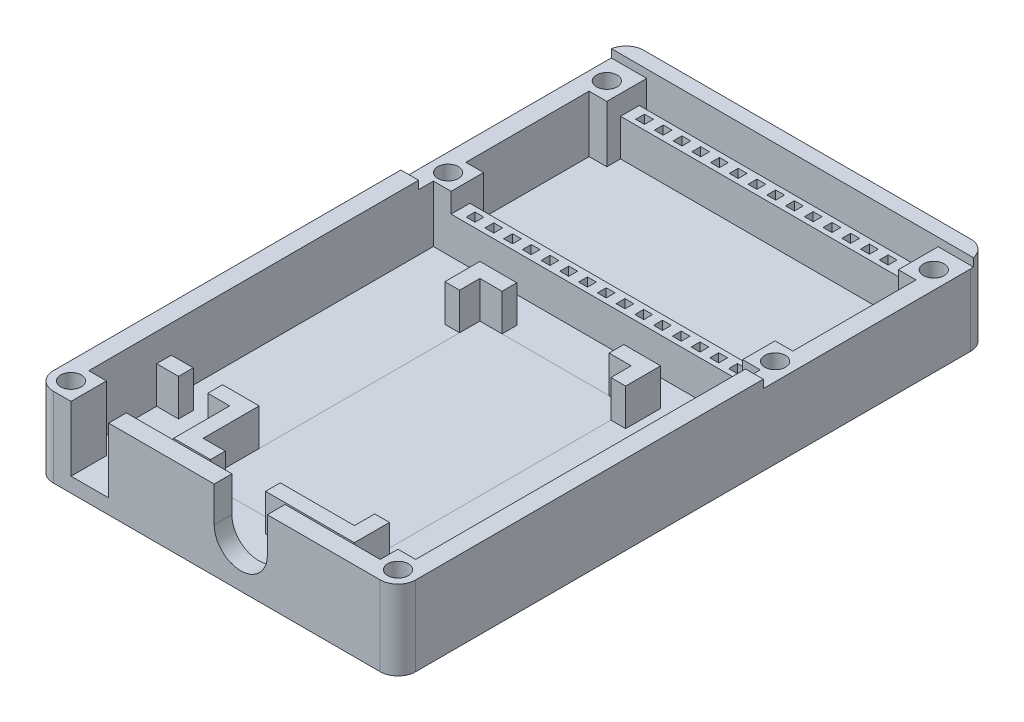
SolidWorks part; units mm, degrees
ref_plane "Front Plane" through (0, 0, 0) normal (0, 0, 1) x (1, 0, 0)
ref_plane "Top Plane" through (0, 0, 0) normal (0, 1, 0) x (1, 0, 0)
ref_plane "Right Plane" through (0, 0, 0) normal (1, 0, 0) x (0, 0, -1)
sketch "Sketch1" plane through (0, 0, 0) normal (0, 1, 0) x (1, 0, 0)
  line L1 (0, 0) -> (49.1, 0)
  line L2 (0, 0) -> (0, -80)
  line L3 (0, -80) -> (49.1, -80)
  line L4 (49.1, 0) -> (49.1, -80)
  dimension "D1" = 49.1
  dimension "D2" = 80
extrude "Boss-Extrude1" add sketch "Sketch1" along normal blind 2
sketch "Sketch2" plane through (0, 2, 0) normal (0, 1, 0) x (1, 0, 0)
  line L0 (24.55, 0) -> (24.55, -5) construction
  line L1 (2.4, -5) -> (46.7, -5) construction
  line L2 (2.4, -5) -> (2.4, -26.5) construction
  line L3 (2.4, -26.5) -> (46.7, -26.5) construction
  line L4 (46.7, -5) -> (46.7, -26.5) construction
  line L5 (49.1, 0) -> (0, 0) construction
  line L6 (0, 0) -> (0, -80) construction
  circle A0 centre (2.4, -5) radius 1.4
  circle A1 centre (46.7, -5) radius 1.4
  circle A2 centre (46.7, -26.5) radius 1.4
  circle A3 centre (2.4, -26.5) radius 1.4
  dimension "D3" = 2.8
  dimension "D1" = 44.3
  dimension "D2" = 21.5
  dimension "D4" = 5
  dimension "D5" = 2.4
extrude "Cut-Extrude1" cut sketch "Sketch2" against normal blind 2
sketch "Sketch3" plane through (0, 2, 0) normal (0, 1, 0) x (1, 0, 0)
  line L0 (2.4, -15.75) -> (46.7, -15.75) construction
  line L1 (2.4, -5) -> (46.7, -5) construction
  line L2 (2.4, -5) -> (2.4, -26.5) construction
  line L3 (2.4, -26.5) -> (46.7, -26.5) construction
  line L4 (46.7, -5) -> (46.7, -26.5) construction
  line L5 (6.17, -3.67) -> (7.37, -3.67)
  line L6 (6.17, -3.67) -> (6.17, -4.87)
  line L7 (6.17, -4.87) -> (7.37, -4.87)
  line L8 (7.37, -3.67) -> (7.37, -4.87)
  line L9 (5.5, -3) -> (8.04, -5.54) construction
  line L10 (5.5, -3) -> (8.04, -3) construction
  line L11 (5.5, -3) -> (5.5, -5.54) construction
  line L12 (5.5, -5.54) -> (8.04, -5.54) construction
  line L13 (8.04, -3) -> (8.04, -5.54) construction
  line L14 (8.04, -3) -> (5.5, -5.54) construction
  line L15 (6.17, -3.67) -> (7.37, -4.87) construction
  line L16 (8.71, -3.67) -> (9.91, -3.67)
  line L17 (8.71, -3.67) -> (8.71, -4.87)
  line L18 (9.91, -3.67) -> (9.91, -4.87)
  line L19 (8.71, -4.87) -> (9.91, -4.87)
  line L20 (11.25, -3.67) -> (12.45, -3.67)
  line L21 (11.25, -3.67) -> (11.25, -4.87)
  line L22 (12.45, -3.67) -> (12.45, -4.87)
  line L23 (11.25, -4.87) -> (12.45, -4.87)
  line L24 (13.79, -3.67) -> (14.99, -3.67)
  line L25 (13.79, -3.67) -> (13.79, -4.87)
  line L26 (14.99, -3.67) -> (14.99, -4.87)
  line L27 (13.79, -4.87) -> (14.99, -4.87)
  line L28 (16.33, -3.67) -> (17.53, -3.67)
  line L29 (16.33, -3.67) -> (16.33, -4.87)
  line L30 (17.53, -3.67) -> (17.53, -4.87)
  line L31 (16.33, -4.87) -> (17.53, -4.87)
  line L32 (18.87, -3.67) -> (20.07, -3.67)
  line L33 (18.87, -3.67) -> (18.87, -4.87)
  line L34 (20.07, -3.67) -> (20.07, -4.87)
  line L35 (18.87, -4.87) -> (20.07, -4.87)
  line L36 (21.41, -3.67) -> (22.61, -3.67)
  line L37 (21.41, -3.67) -> (21.41, -4.87)
  line L38 (22.61, -3.67) -> (22.61, -4.87)
  line L39 (21.41, -4.87) -> (22.61, -4.87)
  line L40 (23.95, -3.67) -> (25.15, -3.67)
  line L41 (23.95, -3.67) -> (23.95, -4.87)
  line L42 (25.15, -3.67) -> (25.15, -4.87)
  line L43 (23.95, -4.87) -> (25.15, -4.87)
  line L44 (26.49, -3.67) -> (27.69, -3.67)
  line L45 (26.49, -3.67) -> (26.49, -4.87)
  line L46 (27.69, -3.67) -> (27.69, -4.87)
  line L47 (26.49, -4.87) -> (27.69, -4.87)
  line L48 (29.03, -3.67) -> (30.23, -3.67)
  line L49 (29.03, -3.67) -> (29.03, -4.87)
  line L50 (30.23, -3.67) -> (30.23, -4.87)
  line L51 (29.03, -4.87) -> (30.23, -4.87)
  line L52 (31.57, -3.67) -> (32.77, -3.67)
  line L53 (31.57, -3.67) -> (31.57, -4.87)
  line L54 (32.77, -3.67) -> (32.77, -4.87)
  line L55 (31.57, -4.87) -> (32.77, -4.87)
  line L56 (34.11, -3.67) -> (35.31, -3.67)
  line L57 (34.11, -3.67) -> (34.11, -4.87)
  line L58 (35.31, -3.67) -> (35.31, -4.87)
  line L59 (34.11, -4.87) -> (35.31, -4.87)
  line L60 (36.65, -3.67) -> (37.85, -3.67)
  line L61 (36.65, -3.67) -> (36.65, -4.87)
  line L62 (37.85, -3.67) -> (37.85, -4.87)
  line L63 (36.65, -4.87) -> (37.85, -4.87)
  line L64 (39.19, -3.67) -> (40.39, -3.67)
  line L65 (39.19, -3.67) -> (39.19, -4.87)
  line L66 (40.39, -3.67) -> (40.39, -4.87)
  line L67 (39.19, -4.87) -> (40.39, -4.87)
  line L68 (41.73, -3.67) -> (42.93, -3.67)
  line L69 (41.73, -3.67) -> (41.73, -4.87)
  line L70 (42.93, -3.67) -> (42.93, -4.87)
  line L71 (41.73, -4.87) -> (42.93, -4.87)
  line L72 (6.17, -27.83) -> (7.37, -26.63) construction
  line L73 (8.04, -28.5) -> (5.5, -25.96) construction
  line L74 (8.04, -28.5) -> (8.04, -25.96) construction
  line L75 (5.5, -25.96) -> (8.04, -25.96) construction
  line L76 (5.5, -28.5) -> (5.5, -25.96) construction
  line L77 (5.5, -28.5) -> (8.04, -28.5) construction
  line L78 (5.5, -28.5) -> (8.04, -25.96) construction
  line L79 (2.4, -26.5) -> (46.7, -26.5) construction
  line L80 (41.73, -26.63) -> (42.93, -26.63)
  line L81 (42.93, -27.83) -> (42.93, -26.63)
  line L82 (41.73, -27.83) -> (41.73, -26.63)
  line L83 (41.73, -27.83) -> (42.93, -27.83)
  line L84 (39.19, -26.63) -> (40.39, -26.63)
  line L85 (40.39, -27.83) -> (40.39, -26.63)
  line L86 (39.19, -27.83) -> (39.19, -26.63)
  line L87 (39.19, -27.83) -> (40.39, -27.83)
  line L88 (36.65, -26.63) -> (37.85, -26.63)
  line L89 (37.85, -27.83) -> (37.85, -26.63)
  line L90 (36.65, -27.83) -> (36.65, -26.63)
  line L91 (36.65, -27.83) -> (37.85, -27.83)
  line L92 (34.11, -26.63) -> (35.31, -26.63)
  line L93 (35.31, -27.83) -> (35.31, -26.63)
  line L94 (34.11, -27.83) -> (34.11, -26.63)
  line L95 (34.11, -27.83) -> (35.31, -27.83)
  line L96 (31.57, -26.63) -> (32.77, -26.63)
  line L97 (32.77, -27.83) -> (32.77, -26.63)
  line L98 (31.57, -27.83) -> (31.57, -26.63)
  line L99 (31.57, -27.83) -> (32.77, -27.83)
  line L100 (29.03, -26.63) -> (30.23, -26.63)
  line L101 (30.23, -27.83) -> (30.23, -26.63)
  line L102 (29.03, -27.83) -> (29.03, -26.63)
  line L103 (29.03, -27.83) -> (30.23, -27.83)
  line L104 (26.49, -26.63) -> (27.69, -26.63)
  line L105 (27.69, -27.83) -> (27.69, -26.63)
  line L106 (26.49, -27.83) -> (26.49, -26.63)
  line L107 (26.49, -27.83) -> (27.69, -27.83)
  line L108 (23.95, -26.63) -> (25.15, -26.63)
  line L109 (25.15, -27.83) -> (25.15, -26.63)
  line L110 (23.95, -27.83) -> (23.95, -26.63)
  line L111 (23.95, -27.83) -> (25.15, -27.83)
  line L112 (21.41, -26.63) -> (22.61, -26.63)
  line L113 (22.61, -27.83) -> (22.61, -26.63)
  line L114 (21.41, -27.83) -> (21.41, -26.63)
  line L115 (21.41, -27.83) -> (22.61, -27.83)
  line L116 (18.87, -26.63) -> (20.07, -26.63)
  line L117 (20.07, -27.83) -> (20.07, -26.63)
  line L118 (18.87, -27.83) -> (18.87, -26.63)
  line L119 (18.87, -27.83) -> (20.07, -27.83)
  line L120 (16.33, -26.63) -> (17.53, -26.63)
  line L121 (17.53, -27.83) -> (17.53, -26.63)
  line L122 (16.33, -27.83) -> (16.33, -26.63)
  line L123 (16.33, -27.83) -> (17.53, -27.83)
  line L124 (13.79, -26.63) -> (14.99, -26.63)
  line L125 (14.99, -27.83) -> (14.99, -26.63)
  line L126 (13.79, -27.83) -> (13.79, -26.63)
  line L127 (13.79, -27.83) -> (14.99, -27.83)
  line L128 (11.25, -26.63) -> (12.45, -26.63)
  line L129 (12.45, -27.83) -> (12.45, -26.63)
  line L130 (11.25, -27.83) -> (11.25, -26.63)
  line L131 (11.25, -27.83) -> (12.45, -27.83)
  line L132 (8.71, -26.63) -> (9.91, -26.63)
  line L133 (9.91, -27.83) -> (9.91, -26.63)
  line L134 (8.71, -27.83) -> (8.71, -26.63)
  line L135 (8.71, -27.83) -> (9.91, -27.83)
  line L136 (7.37, -27.83) -> (7.37, -26.63)
  line L137 (6.17, -26.63) -> (7.37, -26.63)
  line L138 (6.17, -27.83) -> (6.17, -26.63)
  line L139 (6.17, -27.83) -> (7.37, -27.83)
  line L140 (0, 0) -> (0, -80) construction
  line L141 (4.8, -3) -> (44.3, -3)
  line L142 (0, -3) -> (0, -28.5)
  line L143 (0, -28.5) -> (49.1, -28.5)
  line L144 (49.1, -3) -> (49.1, -28.5)
  line L145 (49.1, -80) -> (49.1, 0) construction
  line L146 (24.55, -15.75) -> (24.55, -7.9718) construction
  line L148 (4.8, -3) -> (4.8, -2.6)
  line L149 (4.8, -2.6) -> (0, -2.6)
  line L150 (0, -3) -> (0, -2.6)
  line L151 (44.3, -2.6) -> (49.1, -2.6)
  line L152 (49.1, -3) -> (49.1, -2.6)
  line L154 (44.3, -3) -> (44.3, -2.6)
  circle A0 centre (2.4, -5) radius 1.4 construction
  circle A1 centre (2.4, -5) radius 1.4
  circle A2 centre (2.4, -26.5) radius 1.4
  circle A3 centre (46.7, -5) radius 1.4
  circle A4 centre (46.7, -26.5) radius 1.4
  circle A5 centre (2.4, -26.5) radius 1.4 construction
  point P12 (6.77, -4.27)
  point P139 (6.77, -27.23)
  dimension "D5" = 2
  dimension "D6" = 3.1
  dimension "D1" = 1.2
  dimension "D2" = 1.2
  dimension "D3" = 2.54
  dimension "D4" = 2.54
  dimension "D8" = 2.54
  dimension "D9" = 2.4
  dimension "D10" = 2.4
  dimension "D7" = 15
extrude "Boss-Extrude2" add sketch "Sketch3" along normal blind 5
sketch "Sketch4" plane through (0, 7, 0) normal (0, 1, 0) x (1, 0, 0)
  line L0 (0, -15.75) -> (49.1, -15.75) construction
  line L1 (0, -2.6) -> (0, -28.5) construction
  line L2 (49.1, -2.6) -> (44.3, -2.6) construction
  line L3 (24.55, -3) -> (24.55, -28.5) construction
  line L4 (44.3, -3) -> (4.8, -3) construction
  line L5 (0, -28.5) -> (49.1, -28.5) construction
  line L6 (0, -28.5) -> (49.1, -28.5) construction
  line L7 (0, -24.1) -> (4.8, -24.1)
  line L8 (0, -24.1) -> (0, -28.5)
  line L9 (0, -28.5) -> (4.8, -28.5)
  line L10 (4.8, -24.1) -> (4.8, -28.5)
  line L11 (49.1, -28.5) -> (44.3, -28.5)
  line L12 (44.3, -24.1) -> (44.3, -28.5)
  line L13 (49.1, -24.1) -> (44.3, -24.1)
  line L14 (49.1, -24.1) -> (49.1, -28.5)
  line L15 (49.1, -7.4) -> (49.1, -3)
  line L16 (49.1, -7.4) -> (44.3, -7.4)
  line L17 (44.3, -7.4) -> (44.3, -3)
  line L20 (4.8, -7.4) -> (4.8, -3)
  line L21 (0, -7.4) -> (4.8, -7.4)
  line L22 (0, -7.4) -> (0, -3)
  line L23 (44.3, -2.6) -> (49.1, -2.6)
  line L24 (0, -2.6) -> (4.8, -2.6)
  line L25 (0, -2.6) -> (0, -3)
  line L27 (4.8, -2.6) -> (4.8, -3)
  line L28 (44.3, -2.6) -> (44.3, -3)
  line L30 (49.1, -2.6) -> (49.1, -3)
  line L31 (49.1, -2.6) -> (49.1, 0) construction
  circle A0 centre (2.4, -5) radius 1.4 construction
  circle A1 centre (2.4, -26.5) radius 1.4
  circle A2 centre (2.4, -26.5) radius 1.4 construction
  circle A3 centre (46.7, -26.5) radius 1.4
  circle A4 centre (2.4, -5) radius 1.4
  circle A5 centre (46.7, -5) radius 1.4
  dimension "D1" = 2.4
  dimension "D2" = 2.4
extrude "Boss-Extrude3" add sketch "Sketch4" along normal blind 2.68
sketch "Sketch5" plane through (0, 2, 0) normal (0, 1, 0) x (1, 0, 0)
  line L0 (0, -52.85) -> (49.1, -52.85) construction
  line L1 (0, -80) -> (49.1, -80) construction
  line L3 (0, -28.5) -> (49.1, -28.5) construction
  line L4 (14.3, -34.1) -> (34.8, -34.1)
  line L5 (14.3, -34.1) -> (14.3, -71.6)
  line L6 (14.3, -71.6) -> (34.8, -71.6)
  line L7 (34.8, -34.1) -> (34.8, -71.6)
  line L8 (14.3, -34.1) -> (34.8, -71.6) construction
  line L9 (14.3, -71.6) -> (34.8, -34.1) construction
  line L10 (12.3, -68.85) -> (17.3, -68.85)
  line L11 (12.3, -32.1) -> (36.8, -32.1)
  line L12 (12.3, -32.1) -> (12.3, -73.6)
  line L13 (12.3, -73.6) -> (36.8, -73.6)
  line L14 (36.8, -32.1) -> (36.8, -73.6)
  line L15 (12.3, -32.1) -> (36.8, -73.6) construction
  line L16 (12.3, -73.6) -> (36.8, -32.1) construction
  line L17 (12.3, -32.1) -> (17.3, -32.1)
  line L18 (12.3, -32.1) -> (12.3, -36.85)
  line L19 (12.3, -36.85) -> (17.3, -36.85)
  line L20 (17.3, -32.1) -> (17.3, -36.85)
  line L21 (17.3, -73.6) -> (17.3, -68.85)
  line L22 (12.3, -73.6) -> (17.3, -73.6)
  line L23 (12.3, -73.6) -> (12.3, -68.85)
  line L24 (24.55, -52.85) -> (24.55, -28.5) construction
  line L25 (36.8, -36.85) -> (31.8, -36.85)
  line L26 (31.8, -32.1) -> (31.8, -36.85)
  line L27 (36.8, -32.1) -> (31.8, -32.1)
  line L28 (36.8, -32.1) -> (36.8, -36.85)
  line L29 (36.8, -73.6) -> (31.8, -73.6)
  line L30 (31.8, -73.6) -> (31.8, -68.85)
  line L31 (36.8, -68.85) -> (31.8, -68.85)
  line L32 (36.8, -73.6) -> (36.8, -68.85)
  line L33 (24.7526, -71.6) -> (24.7526, -73.6)
  line L34 (32.7526, -71.6) -> (32.7526, -73.6)
  line L35 (0, -28.5) -> (0, -80) construction
  point P6 (24.55, -52.85)
  point P13 (24.55, -52.85)
  dimension "D1" = 37.5
  dimension "D2" = 20.5
  dimension "D3" = 6.4
  dimension "D4" = 2
  dimension "D5" = 2
  dimension "D6" = 2.75
  dimension "D7" = 3
  dimension "D8" = 8
extrude "Boss-Extrude4" add sketch "Sketch5" along normal blind 5 contours L20 L11 L12 L19 L5 L4 | L11 L26 L4 L7 L25 L14 | L6 L34 L29 L14 L31 L7 | L13 L21 L6 L5 L10 L12 | L6 L33 L13 L30 | L34 L6 L30 L13 region at (14.2677, 2, 33.9427) region at (34.8323, 2, 33.9427) region at (14.2677, 2, 71.7573) region at (35.1905, 2, 71.6391) region at (28.2763, 2, 72.6) region at (32.2763, 2, 72.6)
sketch "Sketch6" plane through (0, 2, 0) normal (0, 1, 0) x (1, 0, 0)
  line L0 (0, -28.5) -> (0, -80) construction
  line L1 (0, -75.2) -> (4.8, -75.2)
  line L2 (0, -75.2) -> (0, -80)
  line L3 (0, -80) -> (4.8, -80)
  line L4 (4.8, -75.2) -> (4.8, -80)
  line L5 (0, -80) -> (49.1, -80) construction
  line L6 (24.55, -80) -> (24.55, -43.6832) construction
  line L7 (0, -80) -> (4.8, -75.2) construction
  line L8 (49.1, -80) -> (44.3, -75.2) construction
  line L9 (44.3, -75.2) -> (44.3, -80)
  line L10 (49.1, -80) -> (44.3, -80)
  line L11 (49.1, -75.2) -> (49.1, -80)
  line L12 (49.1, -75.2) -> (44.3, -75.2)
  circle A0 centre (2.4, -77.6) radius 1.4
  circle A1 centre (46.7, -77.6) radius 1.4
  dimension "D1" = 2.8
  dimension "D3" = 2.4
  dimension "D2" = 2.4
extrude "Boss-Extrude5" add sketch "Sketch6" along normal blind 8.78
sketch "Sketch7" plane through (0, 2, 0) normal (0, 1, 0) x (1, 0, 0)
  line L0 (4.8, -75.2) -> (0, -75.2) construction
  line L1 (0, -28.5) -> (2.4, -28.5)
  line L2 (0, -28.5) -> (0, -75.2)
  line L3 (0, -75.2) -> (2.4, -75.2)
  line L4 (2.4, -28.5) -> (2.4, -75.2)
  line L5 (44.3, -28.5) -> (49.1, -28.5) construction
  line L6 (49.1, -75.2) -> (46.7, -75.2)
  line L7 (49.1, -75.2) -> (49.1, -28.5)
  line L8 (49.1, -28.5) -> (46.7, -28.5)
  line L9 (46.7, -75.2) -> (46.7, -28.5)
  line L10 (49.1, -2.6) -> (49.1, 0) construction
  line L11 (0, 0) -> (49.1, 0)
  line L12 (0, 0) -> (0, -2)
  line L13 (4.8, -2) -> (44.3, -2)
  line L14 (49.1, 0) -> (49.1, -2)
  line L15 (44.3, -3) -> (4.8, -3) construction
  line L16 (4.8, -80) -> (4.8, -75.2) construction
  line L17 (4.8, -77.6) -> (44.3, -77.6)
  line L18 (4.8, -77.6) -> (4.8, -80)
  line L19 (4.8, -80) -> (44.3, -80)
  line L20 (44.3, -77.6) -> (44.3, -80)
  line L23 (0, -2) -> (0, -2.6)
  line L24 (0, -2.6) -> (4.8, -2.6)
  line L25 (4.8, -2) -> (4.8, -2.6)
  line L26 (49.1, -2.6) -> (44.3, -2.6)
  line L27 (49.1, -2.6) -> (49.1, -2)
  line L29 (44.3, -2.6) -> (44.3, -2)
  line L31 (4.8, -7.4) -> (4.8, -2.6) construction
  line L32 (44.3, -3) -> (44.3, -7.4) construction
  dimension "D1" = 2
  dimension "D2" = 2
  dimension "D3" = 0.4
  dimension "D4" = 0.4
extrude "Boss-Extrude6" add sketch "Sketch7" along normal up to surface (8.78 mm away) up to face at (2.4, 10.78, 77.6)
sketch "Sketch8" plane through (0, 0, 80) normal (0, 0, 1) x (1, 0, 0)
  line L0 (0, 0) -> (49.1, 0) construction
  line L2 (4.8, 8.2) -> (4.8, 2)
  line L3 (4.8, 2) -> (9.9, 2)
  line L4 (9.9, 8.2) -> (9.9, 2)
  line L6 (23, 10) -> (32.6, 10) construction
  line L7 (23, 10) -> (23, 2) construction
  line L8 (23, 2) -> (32.6, 2) construction
  line L9 (32.6, 10) -> (32.6, 2) construction
  line L10 (27.8, 10) -> (27.8, 2) construction
  line L11 (0, 10.78) -> (0, 0) construction
  line L12 (24.2, 6) -> (24.2, 10.78)
  line L13 (0, 10.78) -> (49.1, 10.78) construction
  line L14 (24.2, 10.78) -> (31.4, 10.78)
  line L15 (31.4, 10.78) -> (31.4, 6)
  line L16 (49.1, 10.78) -> (49.1, 0) construction
  line L18 (4.8, 8.2) -> (4.8, 10.78)
  line L19 (4.8, 10.78) -> (9.9, 10.78)
  line L20 (9.9, 8.2) -> (9.9, 10.78)
  line L21 (7.35, 2) -> (7.35, 10.78) construction
  arc A0 (24.2, 6) -> (31.4, 6) centre (27.8, 6) ccw
  dimension "D6" = 7.2
  dimension "D1" = 6.2
  dimension "D2" = 21.3
  dimension "D3" = 2
  dimension "D4" = 4.8
  dimension "D5" = 8
  dimension "D7" = 9.6
  dimension "D8" = 7.35
  dimension "D10" = 5.1
extrude "Cut-Extrude2" cut sketch "Sketch8" against normal blind 2.4
sketch "Sketch11" plane through (0, 2, 0) normal (0, 1, 0) x (1, 0, 0)
  circle A0 centre (2.4, -77.6) radius 1.4
  circle A1 centre (2.4, -77.6) radius 1.4 construction
  circle A2 centre (46.7, -77.6) radius 1.4
  circle A3 centre (46.7, -77.6) radius 1.4 construction
extrude "Cut-Extrude4" cut sketch "Sketch11" against normal blind 2
sketch "Sketch12" plane through (0, 2, 0) normal (0, 1, 0) x (1, 0, 0)
  line L1 (14.3, -34.1) -> (34.8, -34.1)
  line L2 (14.3, -34.1) -> (14.3, -71.6)
  line L3 (14.3, -71.6) -> (34.8, -71.6)
  line L4 (34.8, -34.1) -> (34.8, -71.6)
split line "Split Line1"
sketch "Sketch13" plane through (0, 2, 0) normal (0, 1, 0) x (1, 0, 0)
  line L1 (12.3, -66) -> (9.33, -66)
  line L2 (14.3, -66) -> (14.3, -64)
  line L3 (14.3, -64) -> (9.33, -64)
  line L4 (9.33, -66) -> (9.33, -64)
  line L6 (2.4, -75.2) -> (2.4, -28.5) construction
  line L7 (5.37, -64) -> (2.4, -64)
  line L8 (5.37, -64) -> (5.37, -66)
  line L9 (5.37, -66) -> (2.4, -66)
  line L10 (2.4, -64) -> (2.4, -66)
  line L11 (4.8, -80) -> (4.8, -75.2) construction
  line L12 (6.07, -80) -> (6.07, -62.0456) construction
  line L13 (4.8, -80) -> (9.9, -80) construction
  line L14 (8.63, -80) -> (8.63, -61.6074) construction
  line L15 (9.9, -77.6) -> (9.9, -80) construction
  line L16 (9.9, -80) -> (24.2, -80) construction
  line L17 (14.3, -68.85) -> (14.3, -71.6) construction
  line L20 (14.3, -66) -> (14.3, -68.85)
  line L21 (14.3, -68.85) -> (12.3, -68.85)
  line L22 (12.3, -66) -> (12.3, -68.85)
  dimension "D1" = 0.7
  dimension "D2" = 14
  dimension "D3" = 2
  dimension "D4" = 0.7
  dimension "D5" = 1.27
  dimension "D6" = 1.27
extrude "Boss-Extrude7" add sketch "Sketch13" along normal blind 5
sketch "Sketch14" plane through (0, 7, 0) normal (0, 1, 0) x (1, 0, 0)
  line L0 (49.1, -24.1) -> (44.3, -24.1) construction
  line L1 (49.1, -7.4) -> (46.7, -7.4)
  line L2 (49.1, -7.4) -> (49.1, -24.1)
  line L3 (49.1, -24.1) -> (46.7, -24.1)
  line L4 (46.7, -7.4) -> (46.7, -24.1)
  line L5 (4.8, -24.1) -> (0, -24.1) construction
  line L6 (0, -7.4) -> (2.4, -7.4)
  line L7 (0, -7.4) -> (0, -24.1)
  line L8 (0, -24.1) -> (2.4, -24.1)
  line L9 (2.4, -7.4) -> (2.4, -24.1)
extrude "Boss-Extrude8" add sketch "Sketch14" along normal up to surface (2.68 mm away) up to face at (46.7, 9.68, 26.74)
sketch "Sketch16" plane through (0, 7, 0) normal (0, 1, 0) x (1, 0, 0)
  line L0 (4.8, -5.54) -> (44.3, -5.54) construction
  line L1 (4.8, -7.4) -> (4.8, -3) construction
  line L2 (44.3, -3) -> (44.3, -7.4) construction
  line L3 (44.3, -3) -> (4.8, -3) construction
  line L4 (4.8, -25.96) -> (44.3, -25.96) construction
  line L5 (4.8, -28.5) -> (4.8, -24.1) construction
  line L6 (44.3, -24.1) -> (44.3, -28.5) construction
  line L7 (4.8, -28.5) -> (44.3, -28.5) construction
  line L8 (4.8, -24.1) -> (4.8, -25.96)
  line L9 (4.8, -5.54) -> (44.3, -5.54)
  line L10 (4.8, -5.54) -> (4.8, -7.4)
  line L11 (4.8, -25.96) -> (44.3, -25.96)
  line L12 (44.3, -5.54) -> (44.3, -7.4)
  line L13 (2.4, -7.4) -> (4.8, -7.4)
  line L14 (2.4, -7.4) -> (2.4, -24.1)
  line L15 (2.4, -24.1) -> (4.8, -24.1)
  line L17 (46.7, -7.4) -> (44.3, -7.4)
  line L18 (46.7, -7.4) -> (46.7, -24.1)
  line L19 (46.7, -24.1) -> (44.3, -24.1)
  line L21 (44.3, -24.1) -> (44.3, -25.96)
  dimension "D1" = 2.54
  dimension "D2" = 2.54
extrude "Cut-Extrude5" cut sketch "Sketch16" against normal offset from surface (5 mm away) 2 up to face at (2.4, 0, 79)
sketch "Sketch17" plane through (0, 10.78, 0) normal (0, 1, 0) x (1, 0, 0)
  line L0 (2.4, -75.2) -> (2.4, -28.5) construction
  line L1 (0, -2.6) -> (4.8, -2.6)
  line L2 (0, -2.6) -> (0, -2)
  line L3 (0, -2) -> (4.8, -2)
  line L4 (4.8, -2.6) -> (4.8, -2)
  line L5 (49.1, -2.6) -> (44.3, -2.6)
  line L6 (49.1, -2.6) -> (49.1, -2)
  line L7 (49.1, -2) -> (44.3, -2)
  line L8 (44.3, -2.6) -> (44.3, -2)
  line L9 (0, -28.5) -> (2.4, -28.5)
  line L10 (0, -28.5) -> (0, -30.5)
  line L11 (0, -30.5) -> (2.4, -30.5)
  line L12 (2.4, -28.5) -> (2.4, -30.5)
  line L13 (49.1, -80) -> (49.1, -28.5) construction
  line L14 (46.7, -28.5) -> (49.1, -28.5)
  line L15 (46.7, -28.5) -> (46.7, -30.5)
  line L16 (46.7, -30.5) -> (49.1, -30.5)
  line L17 (49.1, -28.5) -> (49.1, -30.5)
  dimension "D1" = 2
extrude "Cut-Extrude6" cut sketch "Sketch17" against normal up to surface (1.1 mm away) up to face at (2.9333, 9.68, 17.0778)
fillet "Fillet1" radius 2.4 4 edges at (0, 5.39, 80) (49.1, 5.39, 80) (49.1, 5.39, 0) (0, 5.39, 0)
